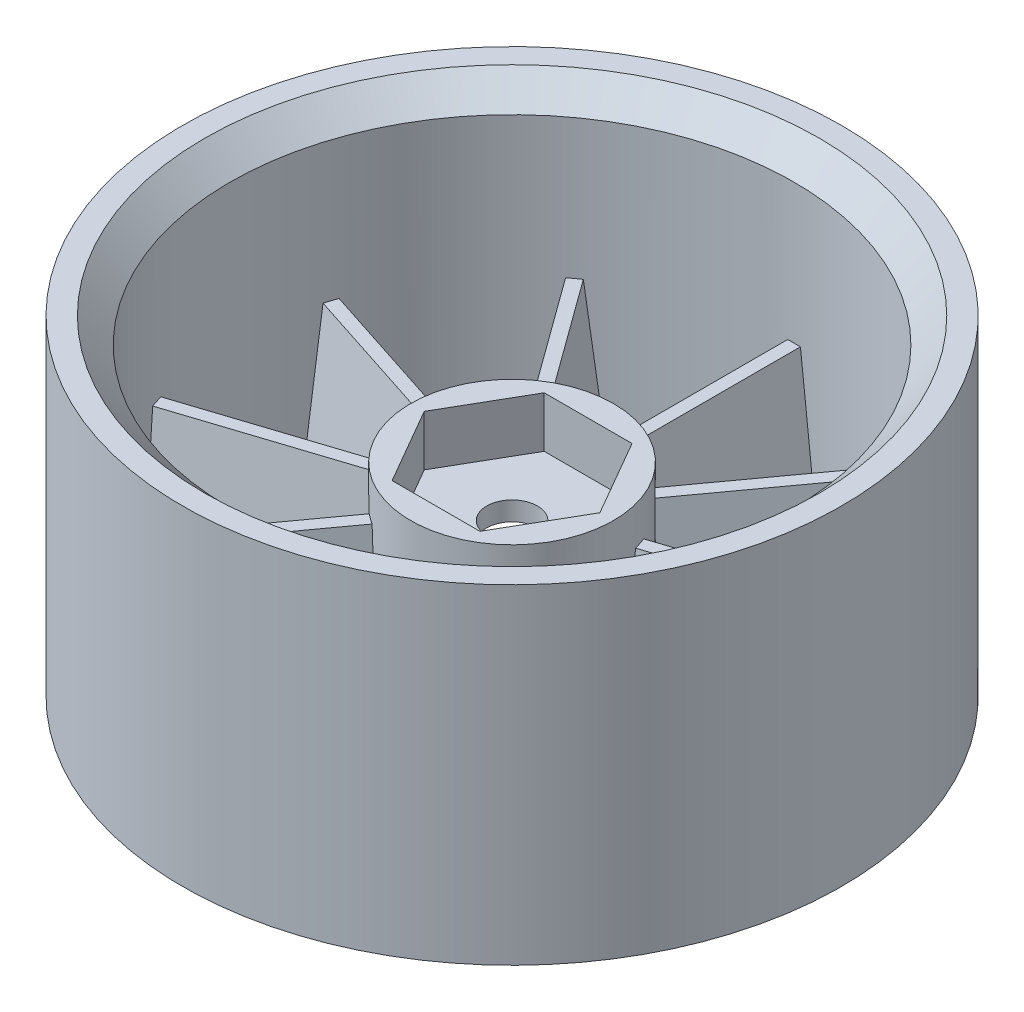
SolidWorks part; units mm, degrees
ref_plane "前视基准面" through (0, 0, 0) normal (0, 0, 1) x (1, 0, 0)
ref_plane "上视基准面" through (0, 0, 0) normal (0, 1, 0) x (1, 0, 0)
ref_plane "右视基准面" through (0, 0, 0) normal (1, 0, 0) x (0, 0, -1)
sketch "草图1" plane through (0, 0, 0) normal (0, 1, 0) x (1, 0, 0)
  circle A0 centre (0, 0) radius 26
  dimension "D1" = 52
extrude "凸台-拉伸1" add sketch "草图1" along normal blind 26
sketch "草图2" plane through (0, 26, 0) normal (0, 1, 0) x (1, 0, 0)
  circle A0 centre (0, 0) radius 22.5
  dimension "D1" = 45
extrude "切除-拉伸1" cut sketch "草图2" against normal through all
chamfer "倒角1" [suppressed] distance 1.5 angle 45
ref_plane "基准面1" through (0, 10, 0) normal (0, -1, 0) x (-1, 0, 0)
sketch "草图3" plane through (0, 10, 0) normal (0, -1, 0) x (-1, 0, 0)
  circle A0 centre (0, 0) radius 8
  dimension "D1" = 16
extrude "凸台-拉伸2" add sketch "草图3" against normal blind 6 separate body
sketch "草图4" plane through (0, 16, 0) normal (0, 1, 0) x (1, 0, 0)
  line L1 (-3.4641, 6) -> (-6.9282, 0)
  line L2 (-6.9282, 0) -> (-3.4641, -6)
  line L3 (-3.4641, -6) -> (3.4641, -6)
  line L4 (3.4641, -6) -> (6.9282, 0)
  line L5 (6.9282, 0) -> (3.4641, 6)
  line L6 (3.4641, 6) -> (-3.4641, 6)
  circle A0 centre (0, 0) radius 6 construction
  dimension "D1" = 12
extrude "切除-拉伸2" cut sketch "草图4" against normal blind 4
sketch "草图5" plane through (0, 0, 0) normal (1, 0, 0) x (0, 0, -1)
  line L0 (22.5, 0) -> (17.5, 0)
  line L1 (-22.5, 0) -> (22.5, 0) construction
  line L2 (-26, 0) -> (26, 0) construction
  line L3 (-28.6, 10) -> (28.6, 10) construction
  line L4 (22.5, 0) -> (22.5, 13)
  line L5 (22.5, 13) -> (7.5, 13)
  line L6 (7.5, 13) -> (7.5, 10)
  line L7 (-22.5, 0) -> (22.5, 0) construction
  line L8 (0, 16) -> (6, 16) construction
  spline S0 degree 2 poles (17.5, 0) (11.3708, 3.8928) (7.5, 10) knots 0 0 0 1 1 1
  point P7 (8.0404, 10)
  point P13 (8.2355, 10)
  dimension "D1" = 5
  dimension "D2" = 15
  dimension "D3" = 3
extrude "凸台-拉伸3" add sketch "草图5" along normal blind 2 and the other way blind 2
sketch "草图6" plane through (0, 0, -7.5) normal (0, 0, 1) x (1, 0, 0)
  line L1 (2, 10) -> (-2, 10)
  line L2 (2, 10) -> (2, 13)
  line L3 (2, 13) -> (-2, 13)
  line L4 (-2, 10) -> (-2, 13)
ref_plane "基准面2" through (0, 0, -7.5) normal (0, 0, 1) x (1, 0, 0)
sketch "草图7" plane through (0, 0, -7.5) normal (0, 0, 1) x (1, 0, 0)
  line L0 (-2, 0) -> (-0.5, 13)
  line L1 (2, 13) -> (-2, 13) construction
  line L2 (-0.5, 13) -> (-2, 13)
  line L3 (-2, 13) -> (-2, 0)
  line L4 (2, 0) -> (0.5018, 13)
  line L5 (0.5018, 13) -> (2, 13)
  line L6 (2, 13) -> (2, 0)
  dimension "D1" = 1.5
  dimension "D2" = 1.4982
extrude "切除-拉伸3" cut sketch "草图7" against normal blind 14.91
fillet "圆角1" radius 10 1 edges at (0, 0, -17.5)
pattern_circular "阵列(圆周)1" count 10 over 360 about axis through (0, 26, 0) along (0, -1, 0) of "凸台-拉伸3", "切除-拉伸3", "圆角1" reverse direction yes
sketch "草图8" plane through (0, 0, 0) normal (0, -1, 0) x (1, 0, 0)
  circle A0 centre (0, 0) radius 22.5
  circle A1 centre (0, 0) radius 22.25
  dimension "D1" = 44.5
extrude "凸台-拉伸5" add sketch "草图8" against normal up to surface (26 mm away) up to face at (0, 26, 22.5)
chamfer "倒角2" distance 2 angle 45 1 edges at (0, 26, 22.25)
sketch "草图9" plane through (0, 10, 0) normal (0, -1, 0) x (-1, 0, 0)
  circle A0 centre (0, 0) radius 6
  dimension "D1" = 12
extrude "切除-拉伸4" cut sketch "草图9" against normal blind 0.5
sketch "草图10" plane through (0, 10.5, 0) normal (0, -1, 0) x (1, 0, 0)
  circle A0 centre (0, 0) radius 2
  dimension "D1" = 4
extrude "切除-拉伸5" cut sketch "草图10" against normal through all
chamfer "倒角3" distance 1 angle 45 10 edges at (-18.0006, 0, 13.0782) (-6.8756, 0, 21.161) (6.8756, 0, 21.161) (18.0006, 0, 13.0782) (22.25, 0, 0) (18.0006, 0, -13.0782) (6.8756, 0, -21.161) (-6.8756, 0, -21.161) (-18.0006, 0, -13.0782) (-22.25, 0, 0)
